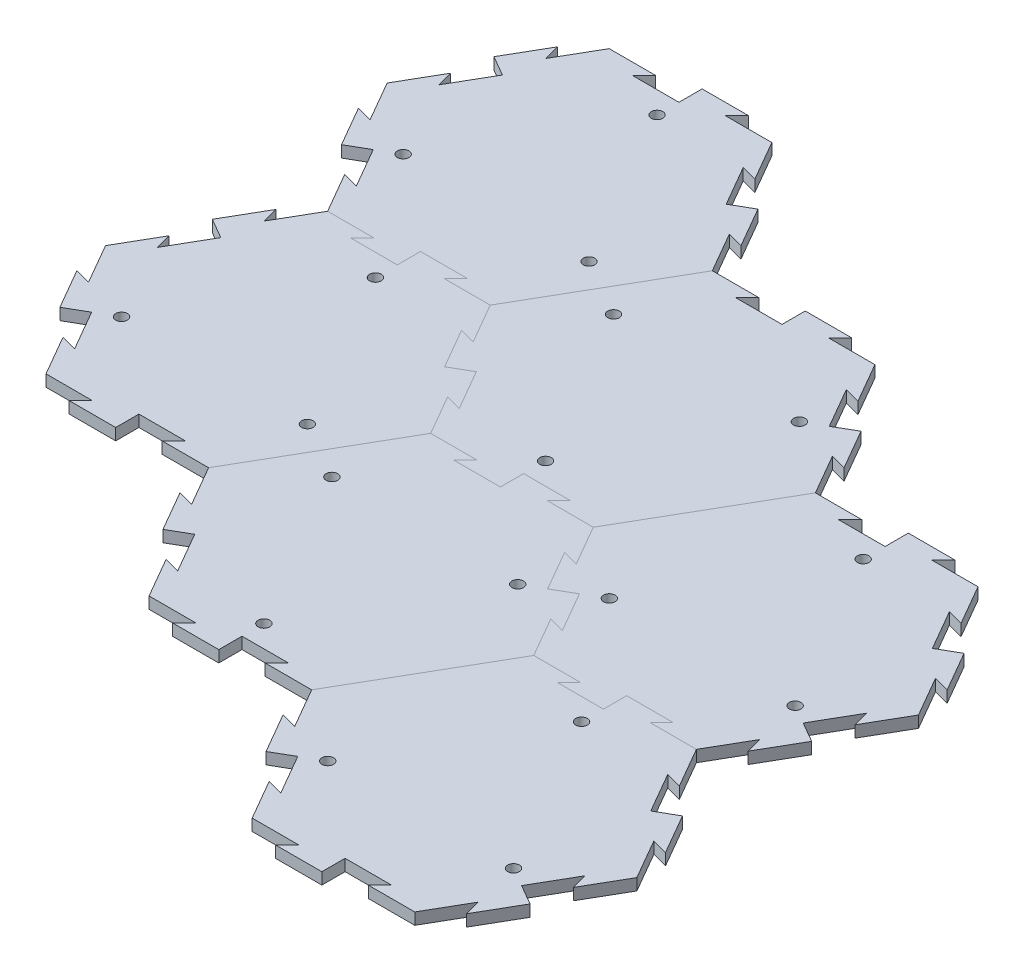
SolidWorks part; units mm, degrees
note: '?' marks a value the reader was unsure of.
material "Cedar"
ref_plane "Front Plane" through (0, 0, 0) normal (0, 0, 1) x (1, 0, 0)
ref_plane "Top Plane" through (0, 0, 0) normal (0, 1, 0) x (1, 0, 0)
ref_plane "Right Plane" through (0, 0, 0) normal (1, 0, 0) x (0, 0, -1)
sketch "Sketch1" plane through (0, 0, 0) normal (0, 1, 0) x (1, 0, 0)
  line L0 (0, 0) -> (88.9, 0) construction
  line L1 (88.9, 0) -> (44.45, 76.9897)
  line L2 (44.45, 76.9897) -> (-44.45, 76.9897)
  line L3 (-44.45, 76.9897) -> (-88.9, 0)
  line L4 (-88.9, 0) -> (-44.45, -76.9897)
  line L5 (-44.45, -76.9897) -> (44.45, -76.9897)
  line L6 (44.45, -76.9897) -> (88.9, 0)
  circle A0 centre (0, 0) radius 76.9897 construction
  dimension "D1" = 88.9
extrude "Boss-Extrude1" add sketch "Sketch1" against normal blind 6.35
sketch "Sketch2" plane through (0, 0, 0) normal (0, 1, 0) x (1, 0, 0)
  point P1 (0, 0)
ref_axis "Axis1" through (0, 0, 0) along (0, 1, 0)?
sketch "Sketch9" plane through (0, 0, 0) normal (0, 1, 0) x (1, 0, 0)
  line L1 (50.8, -29.3294) -> (0, 58.6588) construction
  line L2 (0, 58.6588) -> (-50.8, -29.3294) construction
  line L3 (-50.8, -29.3294) -> (50.8, -29.3294) construction
  circle A0 centre (0, 0) radius 29.3294 construction
  circle A1 centre (-50.8, -29.3294) radius 3.175
  dimension "D2" = 6.35
  dimension "D1" = 101.6
extrude "Cut-Extrude3" cut sketch "Sketch9" against normal through all
pattern_circular "CirPattern6" count 3 over 360 about axis through (0, 0, 0) along (0, 1, 0) of "Cut-Extrude3"
mirror "Mirror3" about plane through (44.45, -6.35, 76.9897) normal (0.866, 0, 0.5) of bodies 121 125
sketch "Sketch10" plane through (0, 0, 0) normal (0, 1, 0) x (1, 0, 0)
  line L0 (44.45, 76.9897) -> (57.15, 54.9926) construction
  line L1 (57.15, 54.9926) -> (48.4757, 57.3169)
  line L2 (48.4757, 57.3169) -> (61.1757, 35.3198)
  line L3 (61.1757, 35.3198) -> (66.675, 38.4948)
  line L4 (57.15, 54.9926) -> (66.675, 38.4948)
  line L5 (88.9, 0) -> (44.45, 76.9897) construction
  dimension "D1" = 45
  dimension "D2" = 6.35
extrude "Cut-Extrude4" cut sketch "Sketch10" against normal through all
sketch "Sketch11" plane through (0, 0, 0) normal (0, 1, 0) x (1, 0, 0)
  line L0 (66.675, 38.4948) -> (88.9, 0) construction
  line L1 (66.675, 38.4948) -> (72.1743, 41.6698)
  line L2 (72.1743, 41.6698) -> (84.8743, 19.6728)
  line L3 (84.8743, 19.6728) -> (76.2, 21.997)
  line L4 (76.2, 21.997) -> (66.675, 38.4948)
  line L5 (76.2, 21.997) -> (88.9, 0) construction
  line L6 (76.2, 21.997) -> (88.9, 0) construction
  line L7 (88.9, 0) -> (66.675, 38.4948) construction
  line L8 (44.45, -76.9897) -> (88.9, 0) construction
  dimension "D1" = 45
  dimension "D2" = 6.35
extrude "Boss-Extrude4" add sketch "Sketch11" against normal blind 6.35 contours L1 L2 L3 L4
pattern_circular "CirPattern7" count 6 over 360 about axis through (0, 0, 0) along (0, 1, 0) skipping 5 of "Cut-Extrude4", "Boss-Extrude4"
mirror "Mirror4" about plane through (222.25, -6.35, 76.9897) normal (0.866, 0, 0.5) of bodies 126 129
sketch "Sketch12" plane through (0, 0, 0) normal (0, 1, 0) x (1, 0, 0)
  line L0 (177.8, 0) -> (88.9, -153.9793) construction
  point P4 (133.35, -76.9897)
ref_axis "Axis2" through (133.35, 0, 76.9897) along (0, 1, 0)?
sketch "Sketch13" plane through (0, 0, 0) normal (0, 1, 0) x (1, 0, 0)
  line L0 (177.8, 0) -> (190.5, -21.997) construction
  line L1 (190.5, -21.997) -> (181.8257, -19.6728)
  line L2 (181.8257, -19.6728) -> (194.5257, -41.6698)
  line L3 (194.5257, -41.6698) -> (200.025, -38.4948)
  line L4 (190.5, -21.997) -> (200.025, -38.4948)
  line L5 (177.8, 0) -> (222.25, -76.9897) construction
  dimension "D1" = 45
  dimension "D2" = 6.35
extrude "Cut-Extrude5" cut sketch "Sketch13" against normal through all
sketch "Sketch14" plane through (0, 0, 0) normal (0, 1, 0) x (1, 0, 0)
  line L0 (200.025, -38.4948) -> (222.25, -76.9897) construction
  line L1 (200.025, -38.4948) -> (205.5243, -35.3198)
  line L2 (205.5243, -35.3198) -> (218.2243, -57.3169)
  line L3 (218.2243, -57.3169) -> (209.55, -54.9926)
  line L4 (209.55, -54.9926) -> (200.025, -38.4948)
  line L5 (209.55, -54.9926) -> (222.25, -76.9897) construction
  line L6 (209.55, -54.9926) -> (222.25, -76.9897) construction
  dimension "D1" = 45
  dimension "D2" = 6.35
extrude "Boss-Extrude5" add sketch "Sketch14" against normal blind 6.35
pattern_circular "CirPattern8" count 6 over 360 about axis through (133.35, 0, 76.9897) along (0, 1, 0) skipping 2, 5 of "Cut-Extrude5", "Boss-Extrude5"
sketch "Sketch15" plane through (0, 0, 0) normal (0, 1, 0) x (1, 0, 0)
  line L0 (311.15, -76.9897) -> (222.25, -230.969) construction
  point P4 (266.7, -153.9793)
ref_axis "Axis3" through (266.7, 0, 153.9793) along (0, 1, 0)?
sketch "Sketch16" plane through (0, 0, 0) normal (0, 1, 0) x (1, 0, 0)
  line L0 (311.15, -76.9897) -> (323.85, -98.9867) construction
  line L1 (323.85, -98.9867) -> (315.1757, -96.6624)
  line L2 (315.1757, -96.6624) -> (327.8757, -118.6595)
  line L3 (327.8757, -118.6595) -> (333.375, -115.4845)
  line L4 (323.85, -98.9867) -> (333.375, -115.4845)
  line L5 (355.6, -153.9793) -> (311.15, -76.9897) construction
  dimension "D1" = 45
  dimension "D2" = 6.35
extrude "Cut-Extrude6" cut sketch "Sketch16" against normal through all
sketch "Sketch17" plane through (0, 0, 0) normal (0, 1, 0) x (1, 0, 0)
  line L0 (333.375, -115.4845) -> (355.6, -153.9793) construction
  line L1 (333.375, -115.4845) -> (338.8743, -112.3095)
  line L2 (338.8743, -112.3095) -> (351.5743, -134.3065)
  line L3 (351.5743, -134.3065) -> (342.9, -131.9823)
  line L4 (342.9, -131.9823) -> (333.375, -115.4845)
  line L5 (342.9, -131.9823) -> (355.6, -153.9793) construction
  line L6 (342.9, -131.9823) -> (355.6, -153.9793) construction
  line L7 (355.6, -153.9793) -> (333.375, -115.4845) construction
  dimension "D1" = 6.35
  dimension "D2" = 45
extrude "Boss-Extrude6" add sketch "Sketch17" against normal up to surface (6.35 mm away) up to face at (320.2496, -6.35, 181.7212)
pattern_circular "CirPattern9" count 6 over 360 about axis through (266.7, 0, 153.9793) along (0, 1, 0) skipping 2 of "Cut-Extrude6", "Boss-Extrude6"
pattern_linear "LPattern1" count 2 spacing 153.9793 along (0, 0, -1) of bodies 125 133 129
